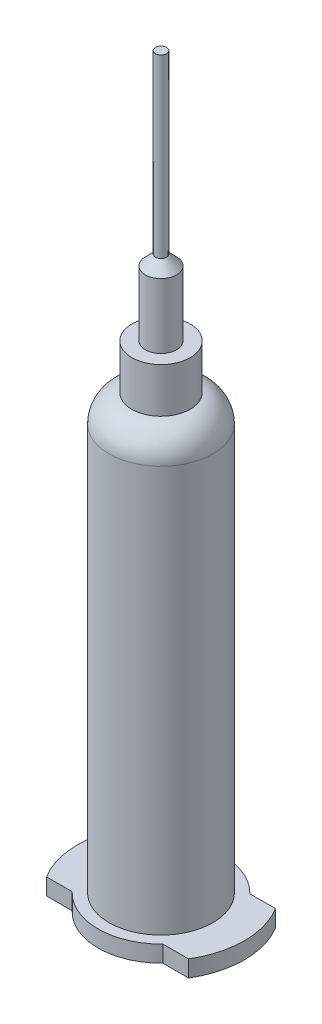
SolidWorks part; units mm, degrees
ref_plane "Front Plane" through (0, 0, 0) normal (0, 0, 1) x (1, 0, 0)
ref_plane "Top Plane" through (0, 0, 0) normal (0, 1, 0) x (1, 0, 0)
ref_plane "Right Plane" through (0, 0, 0) normal (1, 0, 0) x (0, 0, -1)
ref_axis "Axis1" through (-33.0333, 0, 0) along (1, 0, 0)
ref_axis "Axis2" through (0, 24.5224, 0) along (0, -1, 0)
ref_axis "Axis3" through (0, 0, -52.9538) along (0, 0, 1)
sketch "Sketch2" plane through (0, 0, 0) normal (0, 0, 1) x (1, 0, 0)
  line L8 (0, 67.5) -> (0, -67.5)
  line L9 (0, 67.5) -> (1, 67.5)
  line L10 (1, 67.5) -> (1, 35.6)
  line L11 (1, 35.6) -> (2.825, 33.7497)
  line L12 (2.825, 33.7497) -> (2.825, 22)
  line L13 (2.825, 22) -> (5.275, 22)
  line L14 (5.275, 22) -> (5.275, 13.9)
  line L15 (5.275, 13.9) -> (9.4, 13.9)
  line L16 (9.4, 13.9) -> (9.4, -64.5)
  line L17 (9.4, -64.5) -> (15.075, -64.5)
  line L18 (15.075, -64.5) -> (15.075, -67.5)
  line L19 (15.075, -67.5) -> (0, -67.5)
  point P2 (0, 0)
  point P15 (9.4, -64.5163)
  point P16 (2.825, 33.7497)
  dimension "D1" = 135
  dimension "D2" = 1
  dimension "D3" = 31.9
  dimension "D4" = 2.825
  dimension "D5" = 5.275
  dimension "D6" = 9.4
  dimension "D7" = 53.6
  dimension "D8" = 45.5
  dimension "D9" = 3
  dimension "D10" = 15.075
revolve "Revolve1" add sketch "Sketch2" angle 360 about axis through (0, 24.5224, 0) along (0, -1, 0) region at (4.4584, -20.336, 0)
fillet "Fillet1" radius 5 1 edges at (0, 13.9, 9.4)
sketch "Sketch3" plane through (0, -64.5, 0) normal (0, 1, 0) x (1, 0, 0)
  line L0 (-12.8546, 7.875) -> (-8.2082, 7.875)
  line L1 (8.2082, 7.875) -> (12.8546, 7.875)
  line L2 (-111.883, 0) -> (111.883, 0) construction
  line L3 (-12.8546, -7.875) -> (-8.2082, -7.875)
  line L4 (8.2082, -7.875) -> (12.8546, -7.875)
  circle A0 centre (0, 0) radius 15.075 construction
  arc A1 (-8.2082, 7.875) -> (8.2082, 7.875) centre (0, 0) cw
  arc A2 (-12.8546, 7.875) -> (12.8546, 7.875) centre (0, 0) cw
  arc A3 (-8.2082, -7.875) -> (8.2082, -7.875) centre (0, 0) ccw
  arc A4 (-12.8546, -7.875) -> (12.8546, -7.875) centre (0, 0) ccw
  point P16 (-12.8546, 7.875)
  dimension "D2" = 11.375
  dimension "D1" = 15.75
extrude "Cut-Extrude1" cut sketch "Sketch3" against normal up to surface (3 mm away) up to face at (0, -67.5, 15.075)
sketch "Sketch4" plane through (0, -67.5, 0) normal (0, -1, 0) x (1, 0, 0)
  circle A0 centre (0, 0) radius 7.925
  dimension "D1" = 15.85
extrude "Cut-Extrude2" cut sketch "Sketch4" against normal blind 20
